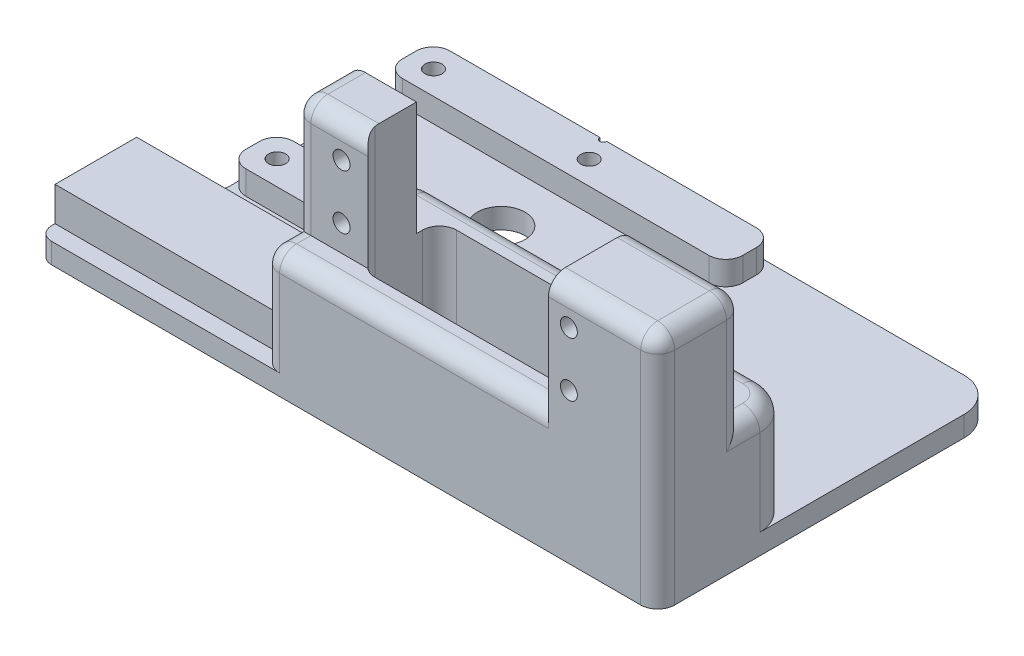
SolidWorks part; units mm, degrees
ref_plane "Front Plane" through (0, 0, 0) normal (0, 0, 1) x (1, 0, 0)
ref_plane "Top Plane" through (0, 0, 0) normal (0, 1, 0) x (1, 0, 0)
ref_plane "Right Plane" through (0, 0, 0) normal (1, 0, 0) x (0, 0, -1)
sketch "Sketch1" plane through (0, 0, 0) normal (0, 1, 0) x (1, 0, 0)
  line L1 (-41.5, 25) -> (41.5, 25)
  line L2 (-41.5, 25) -> (-41.5, -25)
  line L3 (-41.5, -25) -> (41.5, -25)
  line L4 (41.5, 25) -> (41.5, -25)
  line L5 (-41.5, 25) -> (41.5, -25) construction
  line L6 (-41.5, -25) -> (41.5, 25) construction
  point P0 (0, 0)
  dimension "D1" = 50
  dimension "D2" = 83
extrude "Boss-Extrude1" add sketch "Sketch1" along normal blind 3
sketch "Sketch2" plane through (0, 3, 0) normal (0, 1, 0) x (1, 0, 0)
  line L0 (-41.5, 25) -> (-41.5, -25) construction
  line L1 (-41.5, 25) -> (8.5, 25)
  line L2 (-41.5, 25) -> (-41.5, 18)
  line L3 (-41.5, 18) -> (8.5, 18)
  line L4 (8.5, 25) -> (8.5, 18)
  line L5 (-41.5, -5) -> (8.5, -5)
  line L6 (-41.5, -5) -> (-41.5, 2)
  line L7 (-41.5, 2) -> (8.5, 2)
  line L8 (8.5, -5) -> (8.5, 2)
  line L9 (-34.1792, 17.5) -> (16.0708, 17.5) construction
  line L10 (-34.1792, 2.5) -> (7.7462, 2.5) construction
  line L11 (-14, -5) -> (-39, -5) construction
  dimension "D1" = 0.5
  dimension "D2" = 0.5
  dimension "D3" = 50
extrude "Boss-Extrude2" add sketch "Sketch2" along normal up to surface (3.5 mm away)
sketch "Sketch3" plane through (0, 3, 0) normal (0, 1, 0) x (1, 0, 0)
  line L0 (30.9426, -12.4) -> (24.9426, -12.4) construction
  line L1 (41.5, -25) -> (25.4426, -25)
  line L2 (41.5, -25) -> (41.5, -12.4)
  line L3 (41.5, -12.4) -> (25.4426, -12.4)
  line L4 (25.4426, -25) -> (25.4426, -12.4)
  line L5 (-41.5, -25) -> (41.5, -25) construction
  line L6 (-16.5574, -25) -> (-6.5574, -25)
  line L7 (-16.5574, -25) -> (-16.5574, -12.4)
  line L8 (-16.5574, -12.4) -> (-6.5574, -12.4)
  line L9 (-6.5574, -25) -> (-6.5574, -12.4)
  line L10 (-21.6574, -12.4) -> (-15.6574, -12.4) construction
  dimension "D1" = 6.5574
  dimension "D2" = 10
  dimension "D3" = 32
extrude "Boss-Extrude3" add sketch "Sketch3" along normal up to surface (31.93 mm away)
hole_wizard "M3x0.5 Tapped Hole1" positions "Sketch4" profile "Sketch5" tap size "M3x0.5" standard "ANSI Metric" end condition through all
sketch "Sketch4" plane through (0, 0, 12.4) normal (0, 0, -1) x (-1, 0, 0)
  line L0 (16.5574, 34.93) -> (6.5574, 34.93) construction
  line L3 (6.5574, 34.93) -> (-25.4426, 34.93) construction
  line L5 (-9.4426, 34.93) -> (-9.4426, 15.6065) construction
  point P0 (-28.4426, 30.03)
  point P3 (-28.4426, 22.03)
  point P6 (9.5574, 22.03)
  point P9 (9.5574, 30.03)
  point P35 (0, 0)
  dimension "D1" = 4.9
  dimension "D2" = 38
  dimension "D3" = 8
sketch "Sketch5" plane through (28.4426, 30.03, 12.4) normal (1, 0, 0) x (0, 1, 0)
  line L0 (0, 0) -> (0, 12.6)
  line L1 (0, 12.6) -> (1.25, 12.6)
  line L2 (1.25, 12.6) -> (1.25, 0)
  line L5 (1.25, 0) -> (0, 0)
  line L11 (0, -6.35) -> (0, 107.95) construction
  dimension "Thru Tap Drill Dia." = 2.5
  dimension "Thru Tap Drill Depth" = 12.6
cosmetic thread "Hole Thread1" parameters "D2"=3
cosmetic thread "Hole Thread2" parameters "D2"=3
cosmetic thread "Hole Thread3" parameters "D2"=3
cosmetic thread "Hole Thread4" parameters "D2"=3
sketch "Sketch6" plane through (0, 3, 0) normal (0, 1, 0) x (1, 0, 0)
  line L5 (41.5, -25) -> (-16.5574, -25)
  line L6 (41.5, -25) -> (41.5, -5)
  line L7 (41.5, -5) -> (-16.5574, -5)
  line L8 (-16.5574, -25) -> (-16.5574, -5)
  line L9 (-16.5574, -25) -> (-16.5574, -12.4) construction
  line L10 (-41.5, -5) -> (8.5, -5) construction
extrude "Boss-Extrude4" add sketch "Sketch6" along normal offset from surface (15.18 mm away) 16.75 up to face at (33.4713, 34.93, 18.7)
sketch "Sketch10" plane through (0, 18.18, 0) normal (0, 1, 0) x (1, 0, 0)
  line L0 (25.4426, -25) -> (25.4426, -12.4) construction
  line L1 (-6.5574, -21) -> (25.4426, -21)
  line L2 (-6.5574, -21) -> (-6.5574, -9)
  line L3 (-6.5574, -9) -> (25.4426, -9)
  line L4 (25.4426, -21) -> (25.4426, -9)
  line L5 (41.5, -5) -> (-16.5574, -5) construction
  line L7 (-6.5574, -12.4) -> (-6.5574, -25) construction
  line L8 (-6.5574, -25) -> (25.4426, -25) construction
  dimension "D1" = 4
  dimension "D2" = 4
extrude "Cut-Extrude2" cut sketch "Sketch10" against normal up to surface (15.18 mm away) up to face at (-29.0287, 3, 15)
sketch "Sketch12" plane through (0, 34.93, 0) normal (0, 1, 0) x (1, 0, 0)
  line L0 (-6.5574, -12.4) -> (-6.5574, -25) construction
  line L1 (-16.5574, -25) -> (-6.5574, -25)
  line L2 (-16.5574, -25) -> (-16.5574, -20.4)
  line L3 (-16.5574, -20.4) -> (-6.5574, -20.4)
  line L4 (-6.5574, -25) -> (-6.5574, -20.4)
  line L5 (-16.5574, -12.4) -> (-6.5574, -12.4) construction
  dimension "D1" = 8
extrude "Cut-Extrude4" cut sketch "Sketch12" against normal up to surface (16.75 mm away) up to face at (9.4426, 18.18, 23)
sketch "Sketch13" plane through (-16.5574, 0, 0) normal (-1, 0, 0) x (0, 0, 1)
  line L0 (-25, 0) -> (25, 0) construction
  line L1 (10.5, 0) -> (22.5, 0)
  line L2 (10.5, 0) -> (10.5, 8)
  line L3 (10.5, 8) -> (22.5, 8)
  line L4 (22.5, 0) -> (22.5, 8)
  line L5 (25, 18.18) -> (25, 3) construction
  dimension "D1" = 2.5
  dimension "D2" = 12
  dimension "D3" = 8
extrude "Boss-Extrude5" add sketch "Sketch13" along normal blind 33
sketch "Sketch14" plane through (-41.5, 0, 0) normal (-1, 0, 0) x (0, 0, 1)
  line L0 (5, 3) -> (10.5, 3) construction
  line L1 (25, 0) -> (7, 0)
  line L2 (25, 0) -> (25, 3)
  line L3 (25, 3) -> (7, 3)
  line L4 (7, 0) -> (7, 3)
  dimension "D1" = 18
extrude "Boss-Extrude6" add sketch "Sketch14" along normal up to surface (8.0574 mm away) up to face at (-49.5574, 4, 16.5)
fillet "Fillet1" radius 5 3 edges at (41.5, 10.59, 5) (8.5, 4.75, 5) (-16.5574, 4.75, 5)
fillet "Fillet2" radius 5 2 edges at (-16.5574, 12.34, 5) (41.5, 1.5, -25)
fillet "Fillet3" radius 2.5 7 edges at (8.5, 4.75, -18) (-41.5, 4.75, -18) (-41.5, 4.75, -2) (8.5, 4.75, -2) (8.5, 4.75, -25) (-41.5, 4.75, 5) (-41.5, 3.25, -25)
fillet "Fillet4" radius 2.5 5 edges at (41.5, 18.18, 11.2) (40.0355, 18.18, 6.4645) (12.4713, 18.18, 5) (-15.093, 18.18, 6.4645) (4.4426, 18.18, 25)
fillet "Fillet5" radius 2.5 12 edges at (-16.5574, 34.93, 16.4) (-16.5574, 26.555, 20.4) (-11.5574, 34.93, 20.4) (-16.5574, 18.18, 21.45) (-16.5574, 3, 23.75) (-16.5574, 9.34, 25) (-16.5574, 17.4478, 24.2678) (40.7678, 17.4478, 12.4) (33.4713, 34.93, 25) (41.5, 25.305, 12.4) (41.5, 34.93, 18.7) (41.5, 17.465, 25)
hole_wizard "M3x0.5 Tapped Hole2" positions "Sketch7" profile "Sketch8" tap size "M3x0.5" standard "ANSI Metric" end condition through all
sketch "Sketch7" plane through (0, 6.5, 0) normal (0, 1, 0) x (1, 0, 0)
  point P0 (-37.9955, -1.4337)
  point P3 (-15.0663, -1.4955)
  point P6 (-15.0045, 21.4337)
  point P9 (-37.9337, 21.4955)
sketch "Sketch8" plane through (-37.9955, 6.5, 1.4337) normal (1, 0, 0) x (0, 0, 1)
  line L0 (0, 0) -> (0, 6.5)
  line L1 (0, 6.5) -> (1.25, 6.5)
  line L2 (1.25, 6.5) -> (1.25, 0)
  line L5 (1.25, 0) -> (0, 0)
  line L11 (0, -6.35) -> (0, 107.95) construction
  dimension "Thru Tap Drill Dia." = 2.5
  dimension "Thru Tap Drill Depth" = 6.5
cosmetic thread "Hole Thread5" parameters "D2"=3
cosmetic thread "Hole Thread6" parameters "D2"=3
cosmetic thread "Hole Thread7" parameters "D2"=3
cosmetic thread "Hole Thread8" parameters "D2"=3
sketch "Sketch9" plane through (0, 3, 0) normal (0, 1, 0) x (1, 0, 0)
  line L0 (-26.5, 10) -> (-16.5, 10) construction
  circle A0 centre (-16.5, 10) radius 3.5
  dimension "D2" = 7
  dimension "D1" = 10
extrude "Cut-Extrude1" cut sketch "Sketch9" against normal through all
fillet "Fillet6" radius 2.5 8 edges at (-6.5574, 3, 15) (9.4426, 3, 21) (25.4426, 3, 15) (9.4426, 3, 9) (25.4426, 10.59, 21) (25.4426, 10.59, 9) (-6.5574, 10.59, 21) (-6.5574, 10.59, 9)
sketch "Sketch11" plane through (0, 0, 0) normal (0, -1, 0) x (1, 0, 0)
  line L0 (36.5, -25) -> (-39, -25) construction
  line L1 (-17, -25) -> (-16, -25)
  line L2 (-16.5, -10) -> (-16.5, -25) construction
  arc A0 (-17, -25) -> (-16, -25) centre (-16.5, -25) cw
  dimension "D1" = 0.5
extrude "Cut-Extrude3" cut sketch "Sketch11" against normal through all
fillet "Fillet7" radius 2 3 edges at (-49.5574, 1.5, 25) (-41.5, 1.5, 7) (-49.5574, 1.5, 7)
hole_wizard "M3x0.5 Tapped Hole3" positions "Sketch15" profile "Sketch16" tap size "M3x0.5" standard "ANSI Metric" end condition through all
sketch "Sketch15" plane through (0, 0, 0) normal (0, -1, 0) x (-1, 0, 0)
  point P0 (1.5, 10)
  point P3 (31.5, 10)
sketch "Sketch16" plane through (-1.5, 0, -10) normal (1, 0, 0) x (0, 0, -1)
  line L0 (0, 0) -> (0, 34.93)
  line L1 (0, 34.93) -> (1.25, 34.93)
  line L2 (1.25, 34.93) -> (1.25, 0)
  line L5 (1.25, 0) -> (0, 0)
  line L11 (0, -6.35) -> (0, 107.95) construction
  dimension "Thru Tap Drill Dia." = 2.5
  dimension "Thru Tap Drill Depth" = 34.93
cosmetic thread "Hole Thread9" parameters "D2"=3
cosmetic thread "Hole Thread10" parameters "D2"=3
